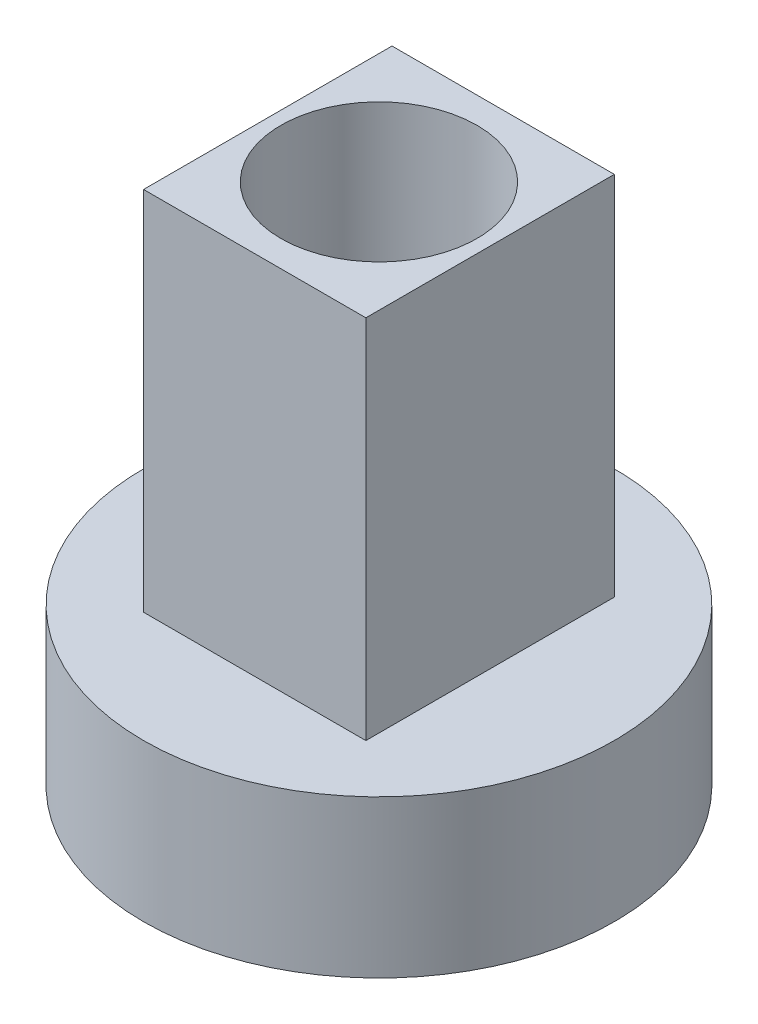
SolidWorks part; units mm, degrees
ref_plane "Спереди" through (0, 0, 0) normal (0, 0, 1) x (1, 0, 0)
ref_plane "Сверху" through (0, 0, 0) normal (0, 1, 0) x (1, 0, 0)
ref_plane "Справа" through (0, 0, 0) normal (1, 0, 0) x (0, 0, -1)
sketch "Эскиз2" plane through (0, 0, 0) normal (0, 1, 0) x (1, 0, 0)
  circle A0 centre (0, 0) radius 90
extrude "Бобышка - Цилиндр" add sketch "Эскиз2" along normal blind 60
sketch "Эскиз4" plane through (0, 60, 0) normal (0, 1, 0) x (1, 0, 0)
  line L1 (-42.5, 47.5) -> (42.5, 47.5)
  line L2 (-42.5, 47.5) -> (-42.5, -47.5)
  line L3 (-42.5, -47.5) -> (42.5, -47.5)
  line L4 (42.5, 47.5) -> (42.5, -47.5)
  line L5 (-42.5, 47.5) -> (42.5, -47.5) construction
  line L6 (-42.5, -47.5) -> (42.5, 47.5) construction
  point P1 (0, 0)
extrude "Бобышка - Паралеллограмм" add sketch "Эскиз4" along normal blind 140
sketch "Эскиз5" plane through (0, 200, 0) normal (0, 1, 0) x (1, 0, 0)
  circle A0 centre (0, 0) radius 37.5
  point P3 (0, 0)
extrude "Вырез центральный" cut sketch "Эскиз5" against normal through all
shell "Оболочка" thickness 3 removed face at (0, 0, 37.5)
